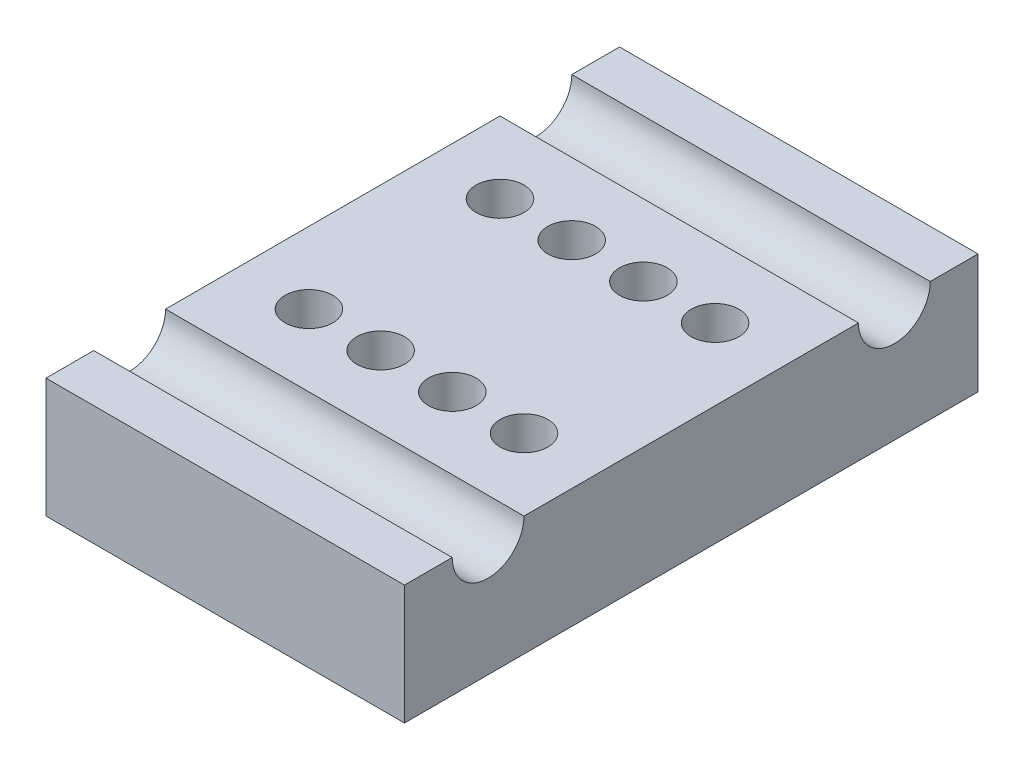
SolidWorks part; units mm, degrees
ref_plane "前视基准面" through (0, 0, 0) normal (0, 0, 1) x (1, 0, 0)
ref_plane "上视基准面" through (0, 0, 0) normal (0, 1, 0) x (1, 0, 0)
ref_plane "右视基准面" through (0, 0, 0) normal (1, 0, 0) x (0, 0, -1)
other "Configuration Table"
sketch "草图1" plane through (0, 0, 0) normal (0, 0, 1) x (1, 0, 0)
  line L1 (0, 0) -> (30, 0)
  line L2 (0, 0) -> (0, 10)
  line L3 (0, 10) -> (30, 10)
  line L4 (30, 0) -> (30, 10)
extrude "凸台-拉伸1" add sketch "草图1" along normal blind 48
sketch "草图3" plane through (0, 0, 0) normal (-1, 0, 0) x (0, 0, 1)
  line L0 (48, 10) -> (0, 10) construction
  line L1 (0, 10) -> (0, 0) construction
  circle A0 centre (7, 10) radius 3.005
  circle A1 centre (41, 10) radius 3.005
  dimension "D1" = 34
  dimension "D2" = 7
extrude "切除-拉伸1" cut sketch "草图3" against normal blind 48
sketch "草图4" plane through (0, 10, 0) normal (0, 1, 0) x (1, 0, 0)
  line L0 (0, -37.995) -> (30, -37.995) construction
  line L1 (30, -10.005) -> (0, -10.005) construction
  line L2 (30, -37.995) -> (30, -10.005) construction
  circle A0 centre (24, -31.995) radius 2
  circle A1 centre (18, -31.995) radius 2
  circle A2 centre (12, -31.995) radius 2
  circle A3 centre (6, -31.995) radius 2
  circle A4 centre (24, -16.005) radius 2
  circle A5 centre (18, -16.005) radius 2
  circle A6 centre (12, -16.005) radius 2
  circle A7 centre (6, -16.005) radius 2
  point P18 (0, 0)
  point P23 (19.7002, -17.7482)
  dimension "D1" = 4
  dimension "D2" = 6
  dimension "D4" = 6
  dimension "D5" = 6
  dimension "D3" = 6
  dimension "D6" = 6
  dimension "D7" = 6
extrude "切除-拉伸2" cut sketch "草图4" against normal through all
